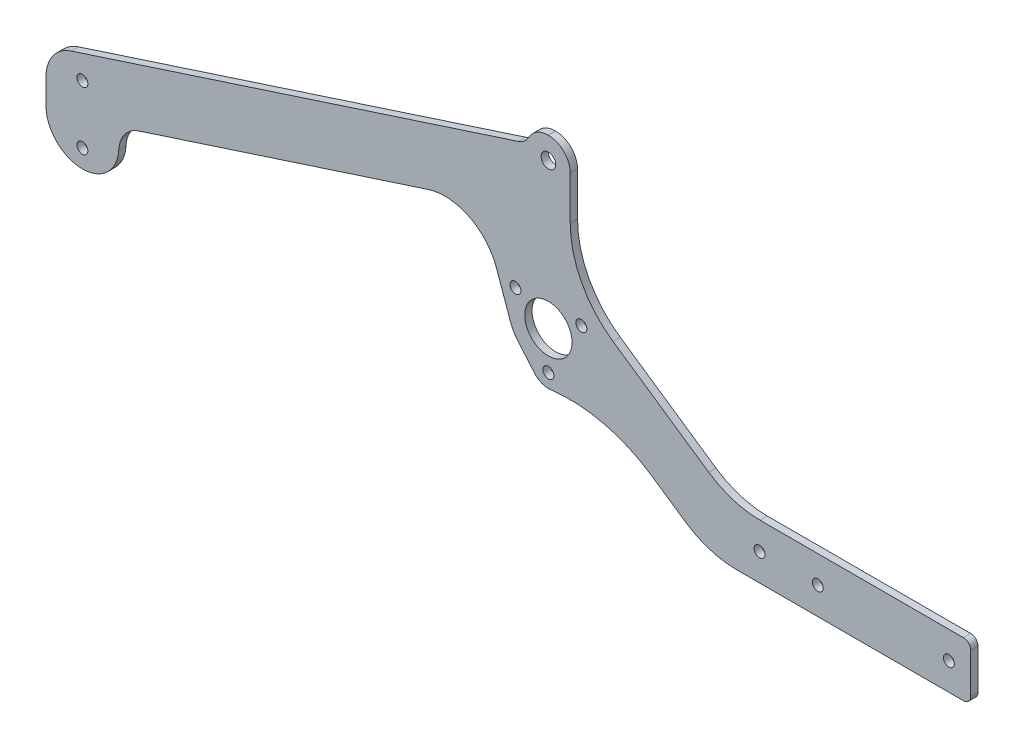
SolidWorks part; units mm, degrees
ref_plane "Спереди" through (0, 0, 0) normal (0, 0, 1) x (1, 0, 0)
ref_plane "Сверху" through (0, 0, 0) normal (0, 1, 0) x (1, 0, 0)
ref_plane "Справа" through (0, 0, 0) normal (1, 0, 0) x (0, 0, -1)
sketch "Эскиз Морковки" plane through (0, 0, 0) normal (0, 0, 1) x (1, 0, 0)
  line L0 (92, -110) -> (92, -24) construction
  line L1 (-53, -110) -> (-53, -24) construction
  line L2 (-198, -24) -> (-164, -24) construction
  line L3 (-198, -110) -> (-53, -110) construction
  line L4 (-198, -24) -> (-216, -24) construction
  line L5 (-53, -110) -> (92, -110) construction
  line L6 (-198, -110) -> (-198, -24) construction
  line L7 (58, -24) -> (92, -24) construction
  line L8 (110, -24) -> (92, -24) construction
  line L9 (-255.5, -110) -> (149.5, -110) construction
  line L10 (-198, -24) -> (-128, -24) construction
  line L11 (-128, -24) -> (-53, -24) construction
  line L12 (-128, -24) -> (0, 0) construction
  line L13 (0, 0) -> (92, -24) construction
  line L14 (-128, -24) -> (-128, -5) construction
  circle A0 centre (-198, -110) radius 57.5 construction
  circle A1 centre (-53, -110) radius 57.5 construction
  circle A2 centre (92, -110) radius 57.5 construction
  circle A3 centre (-216, -24) radius 1.5 construction
  circle A4 centre (-164, -24) radius 1.5 construction
  circle A5 centre (58, -24) radius 1.5 construction
  circle A6 centre (110, -24) radius 1.5 construction
  circle A7 centre (-87, -24) radius 1.5 construction
  circle A8 centre (-35, -24) radius 1.5 construction
  circle A9 centre (-128, -5) radius 1.5
  circle A10 centre (-128, -21) radius 1.5
  circle A11 centre (-128, -36) radius 2
  circle A12 centre (0, 40) radius 2
  circle A13 centre (-180, -24) radius 1.5
  circle A14 centre (74, -24) radius 1.5
  circle A15 centre (-71, -24) radius 1.5
  circle A16 centre (-61, -24) radius 1.5
  circle A17 centre (-45, -24) radius 1.5
  point P31 (-181, -24)
  dimension "D1" = 115
  dimension "D4" = 3
  dimension "D7" = 34
  dimension "D12" = 3
  dimension "D11" = 4
  dimension "D17" = 4
  dimension "D19" = 18
  dimension "D20" = 18
  dimension "D21" = 18
  dimension "D23" = 8
  dimension "D2" = 145
  dimension "D3" = 86
  dimension "D5" = 18
  dimension "D6" = 34
  dimension "D8" = 70
  dimension "D9" = 145
  dimension "D10" = 53
  dimension "D13" = 16
  dimension "D14" = 12
  dimension "D15" = 110
  dimension "D16" = 15
  dimension "D18" = 40
  dimension "D22" = 18
  dimension "D24" = 8
sketch "эскиз 1" plane through (0, 0, 0) normal (0, 0, 1) x (1, 0, 0)
  line L0 (-222, -16.5) -> (-222, -31.5)
  line L1 (-222, -31.5) -> (-152, -31.5)
  line L2 (-152, -31.5) -> (-152, -47)
  line L3 (-222, -16.5) -> (-144.2325, -16.5)
  line L4 (-53, -110) -> (92, -110) construction
  line L5 (-29, -31.5) -> (-29, -16.5)
  line L6 (-152, -47) -> (-104, -47)
  line L9 (-134.245, -27) -> (-121.755, -27)
  line L10 (-104, -31.5) -> (-104, -47)
  line L11 (-53, -16.5) -> (-53, -110) construction
  line L12 (-104, -31.5) -> (-29, -31.5)
  line L13 (-29, -31.5) -> (-104, -31.5)
  line L14 (-138, -26) -> (-118, -26) construction
  line L15 (-111.7675, -16.5) -> (-29, -16.5)
  line L16 (-128, -24) -> (-128, -5) construction
  line L17 (-53, -110) -> (-53, -24) construction
  line L18 (-198, -16.5) -> (-198, -31.5) construction
  line L19 (-198, -110) -> (-198, -24) construction
  line L21 (-128, -27) -> (-128, -47) construction
  line L22 (-138, -27) -> (-138, -16) construction
  line L23 (-118, -26.2682) -> (-118, -16) construction
  line L24 (-144.2325, -16.5) -> (-144.2325, -27) construction
  line L25 (-144.2325, -27) -> (-111.7675, -27) construction
  line L26 (-111.7675, -27) -> (-111.7675, -16.5) construction
  circle A0 centre (-216, -24) radius 1.5
  circle A1 centre (-164, -24) radius 1.5
  circle A2 centre (-128, -36) radius 2
  circle A3 centre (-87, -24) radius 1.5
  circle A4 centre (-35, -24) radius 1.5
  circle A5 centre (-35, -24) radius 1.5 construction
  circle A6 centre (-87, -24) radius 1.5 construction
  circle A7 centre (-128, -36) radius 2 construction
  circle A8 centre (-164, -24) radius 1.5 construction
  circle A9 centre (-216, -24) radius 1.5 construction
  circle A10 centre (-128, -16) radius 10 construction
  circle A11 centre (-128, -36) radius 20 construction
  arc A12 (-121.755, -27) -> (-111.7675, -16.5) centre (-121.755, -17) ccw
  arc A13 (-134.245, -27) -> (-144.2325, -16.5) centre (-134.245, -17) cw
  circle A14 centre (-180, -24) radius 1.5
  circle A15 centre (-180, -24) radius 1.5 construction
  circle A16 centre (-71, -24) radius 1.5
  circle A17 centre (-71, -24) radius 1.5 construction
  point P25 (-128, -47)
  point P33 (-222, -24)
  dimension "D6" = 9
  dimension "D5" = 20
  dimension "D1" = 24
  dimension "D2" = 24
  dimension "D3" = 15
  dimension "D4" = 11
  dimension "D7" = 70
  dimension "D9" = 5
extrude "тело маленькой арки" [suppressed] add sketch "эскиз 1" along normal blind 2
fillet "Скругление2" [suppressed] radius 10
fillet "Скругление3" [suppressed] radius 15
fillet "Скругление16" [suppressed] radius 8
fillet "Скругление18" [suppressed] radius 2
sketch "Эскиз1" plane through (0, 0, 0) normal (0, 0, 1) x (1, 0, 0)
  line L0 (6, 13.8706) -> (50.41, -16.5)
  line L1 (50.41, -16.5) -> (116, -16.5)
  line L2 (116, -16.5) -> (116, -31.5)
  line L3 (116, -31.5) -> (44, -31.5)
  line L4 (44, -31.5) -> (8.372, -7.1351)
  line L5 (-12.7222, 2.951) -> (-10.3652, -3.6828) construction
  line L6 (-10.3652, -3.6828) -> (-19.1717, 21.1032)
  line L7 (6, 13.8706) -> (6, 46)
  line L8 (-131.0902, 0.5106) -> (-6, 41.1548)
  line L9 (-138, -16) -> (-138, -9)
  line L10 (52, -16.5) -> (52, -31.5) construction
  line L11 (-118, -11.0081) -> (-19.1717, 21.1032)
  line L12 (-8.9167, 9.5422) -> (-1.9932, 10.8179) construction
  line L13 (92, -110) -> (92, -24) construction
  line L14 (3.8054, -12.4932) -> (8.372, -7.1351)
  line L15 (-3.8054, -12.4932) -> (-8.372, -7.1351)
  line L16 (-138, -26) -> (-118, -26) construction
  line L17 (-118, -16) -> (-118, -11.0081)
  line L18 (-128, -5) -> (-128, -26) construction
  line L19 (-128, -24) -> (-128, -5) construction
  line L20 (8.9167, 9.5422) -> (1.9932, 10.8179) construction
  line L21 (-118, -26) -> (-118, -16) construction
  line L22 (6, 46) -> (-6, 46)
  line L23 (-138, 1) -> (-118, 1) construction
  line L24 (-6, 46) -> (-6, 41.1548)
  line L27 (12.7222, 2.951) -> (10.3652, -3.6828) construction
  line L31 (-138, -16) -> (-138, -26) construction
  line L32 (-12.7222, 2.951) -> (-10.3652, -3.6828) [skipped]
  circle A0 centre (-128, -21) radius 1.5
  circle A1 centre (-128, -5) radius 1.5
  circle A2 centre (-128, -5) radius 1.5 construction
  circle A3 centre (-128, -21) radius 1.5 construction
  circle A4 centre (0, 0) radius 6.5
  circle A5 centre (0, 0) radius 11 construction
  arc A6 (-8.9167, 9.5422) -> (-12.7222, 2.951) centre (-8.0107, 4.625) ccw construction
  arc A7 (1.9932, 10.8179) -> (-1.9932, 10.8179) centre (0, 0) ccw construction
  arc A8 (-3.8054, -12.4932) -> (3.8054, -12.4932) centre (0, -9.25) ccw
  arc A9 (12.7222, 2.951) -> (8.9167, 9.5422) centre (8.0107, 4.625) ccw construction
  arc A10 (8.372, -7.1351) -> (10.3652, -3.6828) centre (0, 0) ccw construction
  arc A11 (-8.372, -7.1351) -> (-10.3652, -3.6828) centre (0, 0) cw
  circle A12 centre (0, 0) radius 9.25 construction
  circle A13 centre (0, -10.45) radius 1.5
  circle A14 centre (-9.05, 5.225) radius 1.5
  circle A15 centre (9.05, 5.225) radius 1.5
  circle A16 centre (0, 0) radius 7.65 construction
  circle A17 centre (110, -24) radius 1.5
  circle A18 centre (58, -24) radius 1.5
  circle A19 centre (58, -24) radius 1.5 construction
  circle A20 centre (110, -24) radius 1.5 construction
  circle A21 centre (0, 40) radius 2
  circle A22 centre (0, 40) radius 2 construction
  arc A23 (-138, -16) -> (-118, -16) centre (-128, -16) ccw
  arc A24 (-131.0902, 0.5106) -> (-138, -9) centre (-128, -9) ccw
  circle A25 centre (52, -5.6298) radius 25.8702 construction
  circle A26 centre (74, -24) radius 1.5
  circle A27 centre (74, -24) radius 1.5 construction
  point P27 (116, -24)
  point P33 (0, 46)
  point P62 (0, 0)
  point P68 (0, 0)
  dimension "D2" = 13
  dimension "D3" = 3
  dimension "D5" = 5
  dimension "D6" = 18.5
  dimension "D7" = 22
  dimension "D14" = 3
  dimension "D17" = 15.3
  dimension "D18" = 6
  dimension "D20" = 12
  dimension "D13" = 6
  dimension "D22" = 20
  dimension "D4" = 18
  dimension "D11" = 6
  dimension "D16" = 16
  dimension "D9" = 8
  dimension "D1" = 15
  dimension "D8" = 10
  dimension "D10" = 24
  dimension "D12" = 15
  dimension "D15" = 3
  dimension "D19" = 10.45
  dimension "D21" = 5
extrude "тело большой арки" add sketch "Эскиз1" along normal mid plane 2
fillet "Скругление7" radius 15 1 edges at (-19.1717, 21.1032, 0)
fillet "Скругление8" radius 40 1 edges at (8.372, -7.1351, 0)
fillet "Скругление20" radius 6 2 edges at (6, 46, 0) (-6, 46, 0)
fillet "Скругление10" radius 27 1 edges at (6, 13.8706, 0)
fillet "Скругление17" radius 8 1 edges at (-118, -11.0081, 0)
fillet "Скругление21" radius 5 1 edges at (-6, 41.1548, 0)
fillet "Скругление23" radius 2 2 edges at (116, -31.5, 0) (116, -16.5, 0)
fillet "Скругление25" radius 25 2 edges at (50.41, -16.5, 0) (44, -31.5, 0)
